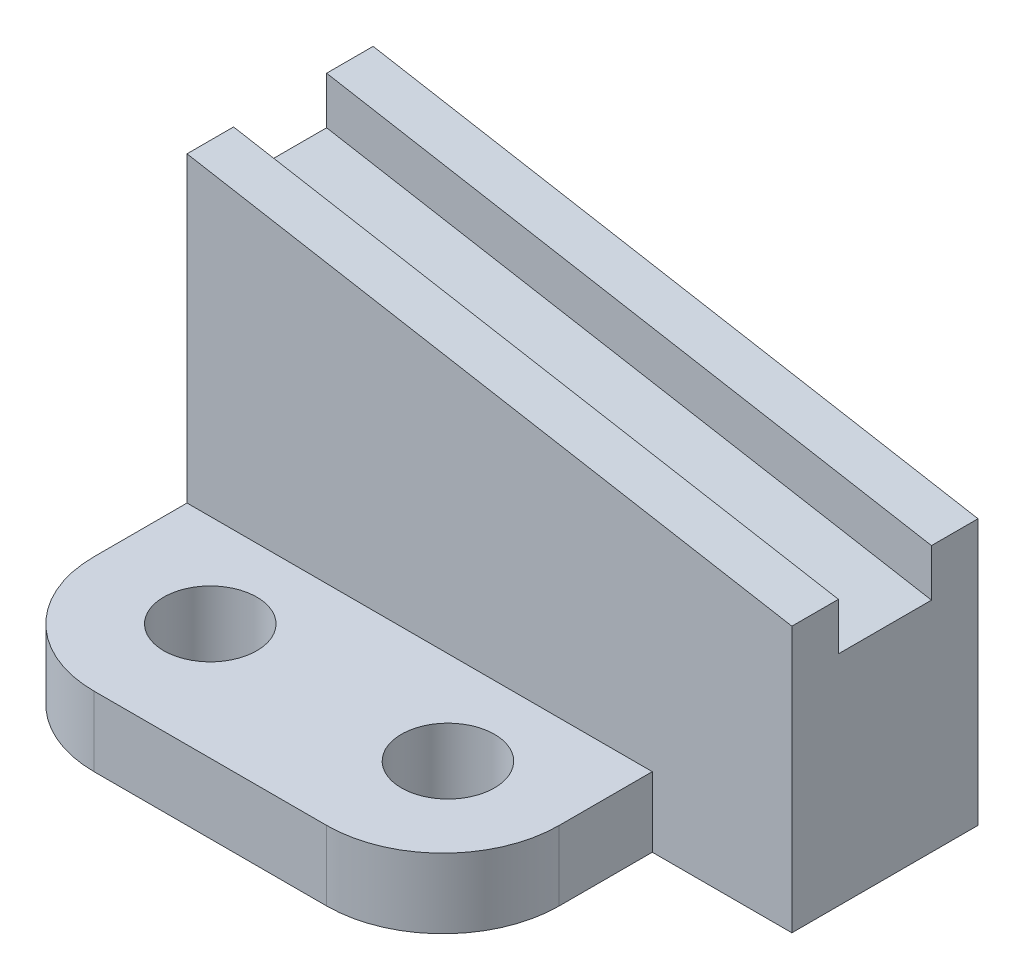
SolidWorks part; units mm, degrees
ref_plane "Plano frontal" through (0, 0, 0) normal (0, 0, 1) x (1, 0, 0)
ref_plane "Plano superior" through (0, 0, 0) normal (0, 1, 0) x (1, 0, 0)
ref_plane "Plano direito" through (0, 0, 0) normal (1, 0, 0) x (0, 0, -1)
sketch "Esboço1" plane through (0, 0, 0) normal (0, 0, 1) x (1, 0, 0)
  line L0 (-53.2953, 9.3008) -> (76.7047, 9.3008)
  line L1 (-53.2953, 9.3008) -> (-53.2953, 89.3008)
  line L2 (76.7047, 9.3008) -> (76.7047, 66.3783)
  line L3 (-53.2953, 89.3008) -> (76.7047, 66.3783)
  dimension "D1" = 100
  dimension "D2" = 80
  dimension "D3" = 130
extrude "Ressalto-extrusão1" add sketch "Esboço1" along normal blind 40
sketch "Esboço3" [suppressed] plane through (13.6643, 77.494, 0) normal (0.1736, 0.9848, 0) x (0.9848, -0.1736, 0)
  line L0 (64.0129, -40) -> (-67.9926, -40) construction
  line L1 (-71.0201, -30) -> (70.4962, -30)
  line L2 (-71.0201, -30) -> (-71.0201, -10)
  line L3 (-71.0201, -10) -> (70.4962, -10)
  line L4 (70.4962, -30) -> (70.4962, -10)
  line L5 (64.0129, 0) -> (-67.9926, 0) construction
  dimension "D1" = 10
  dimension "D2" = 10
extrude "Corte-extrusão2" [suppressed] cut sketch "Esboço3" against normal blind 10
sketch "Esboço4" plane through (13.6643, 77.494, 0) normal (0.1736, 0.9848, 0) x (0.9848, -0.1736, 0)
  line L0 (64.0129, 0) -> (-67.9926, 0) construction
  line L1 (-77.3839, -10) -> (94.2466, -10)
  line L2 (-77.3839, -10) -> (-77.3839, -30)
  line L3 (-77.3839, -30) -> (94.2466, -30)
  line L4 (94.2466, -10) -> (94.2466, -30)
  line L5 (64.0129, -40) -> (-67.9926, -40) construction
  dimension "D1" = 10
  dimension "D2" = 10
extrude "Corte-extrusão3" cut sketch "Esboço4" against normal blind 10
sketch "Esboço5" plane through (0, 0, 40) normal (0, 0, 1) x (1, 0, 0)
  line L1 (-53.2953, 9.3008) -> (46.7047, 9.3008)
  line L2 (-53.2953, 9.3008) -> (-53.2953, 24.3008)
  line L3 (-53.2953, 24.3008) -> (46.7047, 24.3008)
  line L4 (46.7047, 9.3008) -> (46.7047, 24.3008)
  dimension "D1" = 15
  dimension "D2" = 100
extrude "Ressalto-extrusão2" add sketch "Esboço5" along normal blind 45
fillet "Filete6" radius 25 1 edges at (-53.2953, 16.8008, 85) type face fillet first side face at (-53.2953, 61.52, 35.25) second side face at (-3.2953, 16.8008, 85)
fillet "Filete7" radius 25 1 edges at (46.7047, 16.8008, 85) type face fillet first side face at (9.2047, 16.8008, 85) second side face at (46.7047, 14.9258, 68.125)
sketch "Esboço7" plane through (0, 24.3008, 0) normal (0, 1, 0) x (1, 0, 0)
  line L0 (21.7047, -85) -> (-28.2953, -85) construction
  circle A0 centre (-28.2953, -60) radius 10
  circle A1 centre (22.7777, -60) radius 10
  dimension "D1" = 20
  dimension "D2" = 20
  dimension "D3" = 25
extrude "Corte-extrusão4" cut sketch "Esboço7" against normal through all
